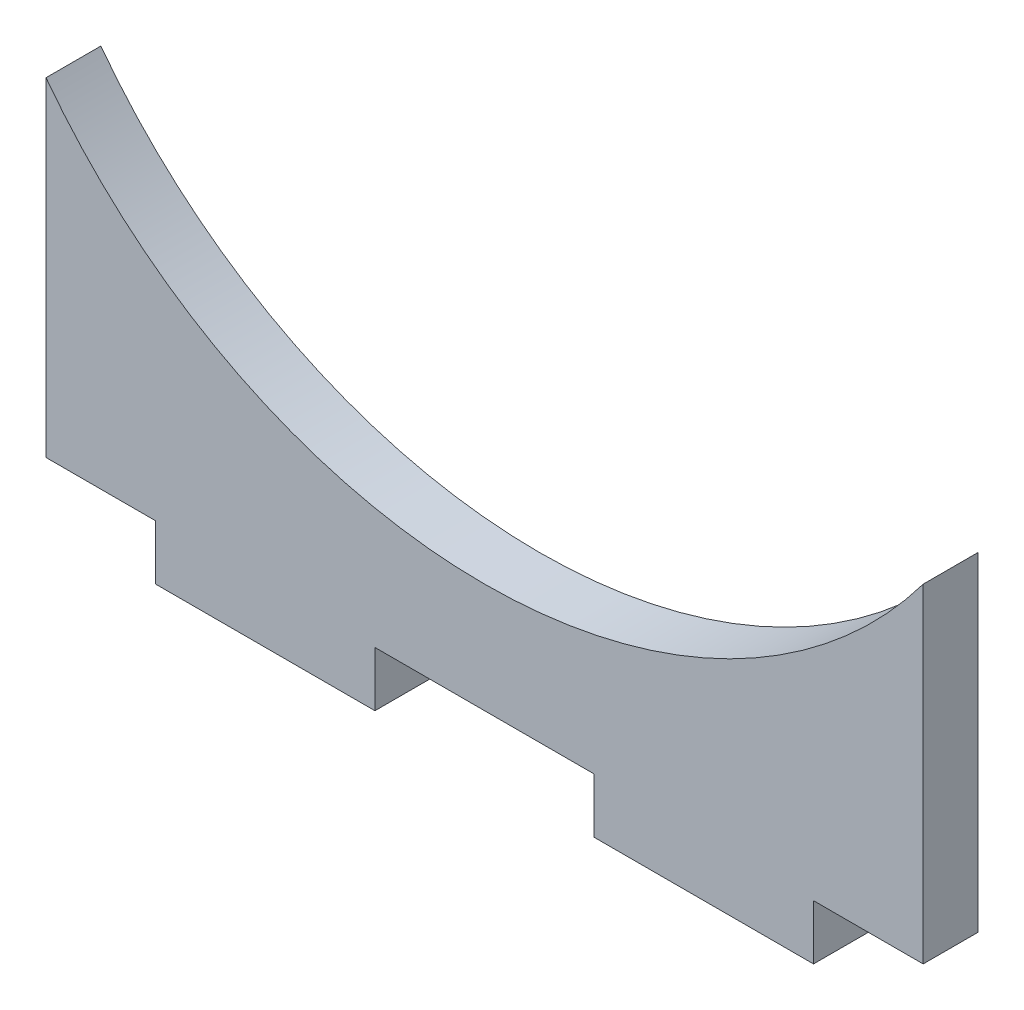
SolidWorks part; units mm, degrees
material "Pine"
ref_plane "Front Plane" through (0, 0, 0) normal (0, 0, 1) x (1, 0, 0)
ref_plane "Top Plane" through (0, 0, 0) normal (0, 1, 0) x (1, 0, 0)
ref_plane "Right Plane" through (0, 0, 0) normal (1, 0, 0) x (0, 0, -1)
sketch "Sketch1" plane through (0, 0, 0) normal (0, 0, 1) x (1, 0, 0)
  line L0 (0, 0) -> (0, 82.55) construction
  line L1 (50.8, 6.35) -> (50.8, 140.462) construction
  line L2 (-50.8, 6.35) -> (-50.8, 140.462) construction
  line L3 (50.8, 6.35) -> (50.8, 44.45)
  line L4 (-50.8, 6.35) -> (-50.8, 44.45)
  line L5 (-50.8, 6.35) -> (-38.1, 6.35)
  line L6 (-12.7, 6.35) -> (12.7, 6.35)
  line L8 (-38.1, 6.35) -> (-38.1, 0)
  line L9 (-38.1, 0) -> (-12.7, 0)
  line L10 (-12.7, 6.35) -> (-12.7, 0)
  line L12 (38.1, 6.35) -> (38.1, 0)
  line L13 (38.1, 0) -> (12.7, 0)
  line L14 (12.7, 6.35) -> (12.7, 0)
  line L15 (38.1, 6.35) -> (50.8, 6.35)
  arc A0 (-50.8, 44.45) -> (50.8, 44.45) centre (0, 82.55) ccw
  dimension "D1" = 63.5
  dimension "D2" = 38.1
extrude "Boss-Extrude1" add sketch "Sketch1" along normal up to surface (6.35 mm away)
